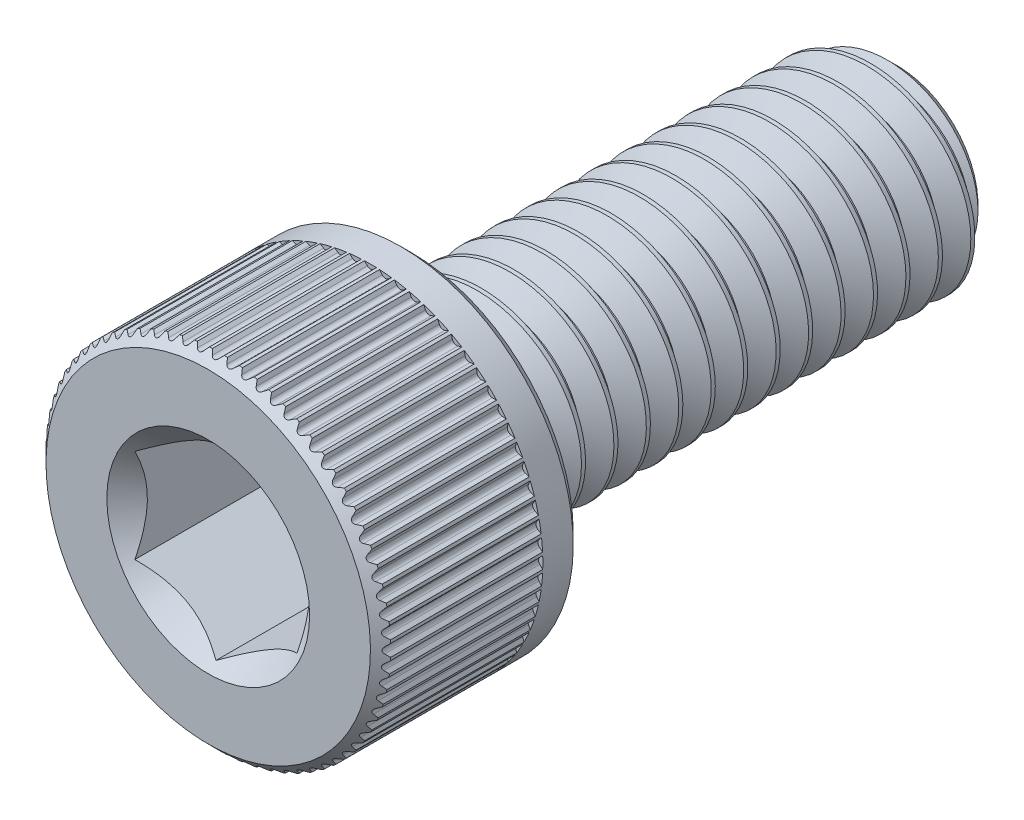
SolidWorks part; units mm, degrees
ref_plane "Front Plane" through (0, 0, 0) normal (0, 0, 1) x (1, 0, 0)
ref_plane "Top Plane" through (0, 0, 0) normal (0, 1, 0) x (1, 0, 0)
ref_plane "Right Plane" through (0, 0, 0) normal (1, 0, 0) x (0, 0, -1)
sketch "Sketch1" plane through (0, 0, 0) normal (1, 0, 0) x (0, 0, -1)
  line L0 (-8.5, 0) -> (8.5, 0) construction
  line L1 (8.5, 0) -> (8.5, 1.9804) construction
  line L2 (8.5, 1.9804) -> (7.9804, 2.5) construction
  line L3 (7.9804, 2.5) -> (7.9, 2.5) construction
  line L4 (7.9, 2.5) -> (-3.5, 2.5) construction
  line L5 (-3.5, 2.5) -> (-3.5, 4.25) construction
  line L6 (-3.5, 4.25) -> (-8.5, 4.25) construction
  line L7 (-8.5, 4.25) -> (-8.5, 0) construction
  line L8 (8.5, 1.9804) -> (8.5, 2.5) construction
  line L9 (8.45, 2.5866) -> (8.85, 1.8938) construction
  line L10 (8.85, 1.8938) -> (9.25, 2.5866) construction
  line L11 (9.25, 2.5866) -> (8.45, 2.5866) construction
  line L12 (8.85, 2.5866) -> (8.85, 2.5) construction
  line L13 (8.85, 1.8938) -> (8.85, 1.9804) construction
  line L14 (8.8, 1.9804) -> (8.9, 1.9804) construction
  line L15 (8.5, 2.5) -> (9.2, 2.5) construction
  line L16 (8.475, 2.5433) -> (9.225, 2.5433) construction
  line L17 (8.5, 0) -> (8.5, -2.5) construction
  line L18 (-3.75, 4.25) -> (-3.5, 4) construction
  line L19 (-8.25, 4.25) -> (-8.5, 4) construction
  line L20 (-3.5, 2.5) -> (-3.5, 0) construction
  line L21 (-3.5, 1.25) -> (0.5, 1.25) construction
  line L22 (0.5, 1.25) -> (4.5, 1.25) construction
  line L23 (4.5, 1.25) -> (8.5, 1.25) construction
  line L24 (0.5, 1.25) -> (0.5, 2.5) construction
  line L25 (0.5, 2.5) -> (0.5, 4.25) construction
  line L26 (4.5, 1.25) -> (4.5, 4.25) construction
  point P0 (-8.5, 2)
  point P3 (6.5, 2.5)
  point P4 (0, 0)
  point P18 (4.5, 2.5)
  point P22 (8.85, 1.9804)
  point P24 (7.9, 2.5)
  point P25 (8.85, 2.5)
  point P28 (8.85, 2.5433)
  point P29 (6.5, -2.5)
  point P30 (0.5, 2.5)
  point P31 (-6, 4.25)
  point P37 (-4.375, 4.25)
  point P38 (-8.125, 4.25)
  point P45 (0.5, 1.25)
  point P46 (4.5, 1.25)
  dimension "D2" = 0.1
  dimension "D7" = 0.25
  dimension "D8" = 0.25
  dimension "D9" = 0.25
  dimension "D10" = 0.125
  dimension "D11" = 0.625
  dimension "Drive Size" = 4
  dimension "Head Diameter" = 8.5
  dimension "Head Height" = 5
  dimension "Thread Pitch" = 0.8
  dimension "Thread Size" = 5
  dimension "Length" = 12
  dimension "D12" = 0.6
  dimension "D4" = 2
  dimension "D3" = 45
sketch "Sketch2" plane through (0, 0, 0) normal (1, 0, 0) x (0, 0, -1)
  line L0 (-8.5, 0) -> (-8.5, 4)
  line L1 (-8.25, 4.25) -> (-3.75, 4.25)
  line L2 (-3.5, 4) -> (-3.5, 2.75)
  line L4 (7.9804, 2.5) -> (8.5, 1.9804)
  line L5 (8.5, 1.9804) -> (8.5, 0)
  line L6 (-3.5, 4.25) -> (-8.5, 4.25) construction
  line L7 (8.5, 0) -> (-8.5, 0)
  line L8 (-8.25, 4.25) -> (-8.5, 4) construction
  line L10 (-8.25, 4.25) -> (-8.5, 4)
  line L14 (-3.75, 4.25) -> (-3.5, 4) construction
  line L16 (-3.75, 4.25) -> (-3.5, 4)
  line L17 (-3.5, 2.5) -> (-3.5, 4.25) construction
  line L19 (-3.25, 2.5) -> (7.9804, 2.5)
  line L20 (7.9, 2.5) -> (-3.5, 2.5) construction
  arc A1 (-3.5, 2.75) -> (-3.25, 2.5) centre (-3.25, 2.75) ccw
  dimension "D3" = 0.25
revolve "Revolve1" add sketch "Sketch2" angle 360 about L7
sketch "Sketch3" plane through (0, 0, 8.5) normal (0, 0, 1) x (1, 0, 0)
  line L1 (2, -1.1547) -> (2, 1.1547)
  line L2 (2, 1.1547) -> (0, 2.3094)
  line L3 (0, 2.3094) -> (-2, 1.1547)
  line L4 (-2, 1.1547) -> (-2, -1.1547)
  line L5 (-2, -1.1547) -> (0, -2.3094)
  line L6 (0, -2.3094) -> (2, -1.1547)
  circle A0 centre (0, 0) radius 2 construction
  circle A1 centre (0, 0) radius 4.25 construction
  circle A2 centre (0, 0) radius 4.25 construction
  circle A3 centre (0, 0) radius 2.3094 construction
  point P13 (0, 0)
extrude "Cut-Extrude1" cut sketch "Sketch3" against normal offset from surface (4 mm away) 1 up to face at (0, 4, 3.5)
sketch "Sketch4" plane through (0, 0, 8.5) normal (0, 0, 1) x (1, 0, 0)
  circle A0 centre (0, 0) radius 2.5
  dimension "D1" = 5
extrude "Cut-Extrude2" cut sketch "Sketch4" against normal up to vertex (2.5 mm away) draft 45
sketch "Sketch11" plane through (0, 0, 0) normal (1, 0, 0) x (0, 0, -1)
  line L0 (-8.5, 0) -> (8.5, 0) construction
  line L1 (-8.5, 0) -> (8.5, 0) construction
  line L2 (-1.25, 0) -> (-1.25, 2.5) construction
  line L3 (7.9, 2.5) -> (-3.5, 2.5) construction
  line L4 (6.25, 0) -> (6.25, 2.5) construction
  line L6 (8.5, 1.9804) -> (8.5, 2.5) construction
  point P2 (-1.25, 0)
  point P3 (6.25, 0)
  dimension "D1" = 2.25
  dimension "D2" = 2.25
sketch "Sketch6" plane through (0, 0, -8.5) normal (0, 0, -1) x (-1, 0, 0)
  circle A0 centre (0, 0) radius 2.5
curve "Helix/Spiral1" pitch 0.8 height 12.8 turns 16
sketch "Sketch10" plane through (0, 0, 0) normal (1, 0, 0) x (0, 0, -1)
  line L0 (-3.25, -4.25) -> (-3.25, 4.25)
  line L5 (-8.5, 0) -> (8.5, 0) construction
  line L6 (-3.25, 2.5) -> (-3.25, -2.5) construction
  point P3 (-3.25, 0)
split "Split1" trim tools "Sketch10" bodies to split 106 resulting bodies 114 115
sketch "Sketch7" plane through (0, 0, 0) normal (1, 0, 0) x (0, 0, -1)
  line L0 (8.475, 2.5433) -> (9.225, 2.5433)
  line L1 (9.225, 2.5433) -> (8.9, 1.9804)
  line L2 (8.9, 1.9804) -> (8.8, 1.9804)
  line L3 (8.8, 1.9804) -> (8.475, 2.5433)
sweep "Cut-Sweep1" cut profiles "Sketch7" path "Helix/Spiral1"
sketch "Sketch8" plane through (0, 0, 0) normal (1, 0, 0) x (0, 0, -1)
  line L0 (-3.5, 0) -> (-3.5, 2.5)
  line L1 (-3.25, -2.5) -> (-3.25, 2.5) construction
  line L2 (-3.5, 2.5) -> (-3.25, 2.5)
  line L4 (-3.25, 2.5) -> (-1.8066, 0)
  line L5 (-1.8066, 0) -> (-3.5, 0)
  line L6 (7.9, 2.5) -> (-3.5, 2.5) construction
  line L7 (-8.5, 0) -> (8.5, 0) construction
  dimension "D1" = 60
revolve "Revolve2" add sketch "Sketch8" angle 360 about L5
ref_plane "Plane1" through (0, 0, 8.5) normal (0, 0, 1) x (1, 0, 0)
sketch "Sketch12" plane through (0, 0, 8.5) normal (0, 0, 1) x (1, 0, 0)
  line L0 (0, 0) -> (0.1483, 4.2474) construction
  line L1 (0, 0) -> (-0.1483, 4.2474) construction
  line L2 (0, 4.1437) -> (0, 4.3563) construction
  line L3 (-0.2572, 4.3563) -> (0.2572, 4.3563)
  line L4 (-0.2572, 4.3563) -> (-0.0762, 4.1753)
  line L5 (0.0762, 4.1753) -> (0.2572, 4.3563)
  circle A0 centre (0, 0) radius 4.25 construction
  arc A1 (-0.0762, 4.1753) -> (0.0762, 4.1753) centre (0, 4.2516) ccw
  point P9 (0, 4.3563)
  point P13 (0, 4.25)
  dimension "D1" = 4
  dimension "D2" = 0.1063
extrude "Cut-Extrude3" cut sketch "Sketch12" against normal blind 4
pattern_circular "CirPattern1" count 72 over 360 about axis through (0, 0, 0) along (0, 0, 1) of "Cut-Extrude3"
equation "\"D2@Sketch1\" = \"Thread Pitch@Sketch1\" / 8"
equation "\"D4@Helix/Spiral1\" = \"Thread Pitch@Sketch1\""
equation "\"D7@Sketch1\" = \"Head Height@Sketch1\" * .05"
equation "\"D8@Sketch1\"=\"D7@Sketch1\""
equation "\"D9@Sketch1\"=\"D7@Sketch1\""
equation "\"D10@Sketch1\"=\"D7@Sketch1\"/2"
equation "\"D11@Sketch1\"=\"D10@Sketch1\"*5"
equation "\"D4@Sketch1\"=\"Thread Pitch@Sketch1\"*2.5"
equation "\"D12@Sketch1\"=\"Thread Pitch@Sketch1\"*.75"
equation "\"D3@Helix/Spiral1\"=\"Length@Sketch1\"+\"Thread Pitch@Sketch1\""
equation "\"D3@Sketch2\" = \"Thread Size@Sketch1\" * 0.05"
equation "\"D1@Sketch11\"=\"Length@Sketch1\"*0.1875"
equation "\"D2@Sketch11\"=\"D1@Sketch11\""
equation "\"D2@Sketch12\"=\"Head Diameter@Sketch1\"*.0125"
equation "\"D1@Cut-Extrude3\"=\"Head Height@Sketch1\"*.8"
equation "\"D1@CirPattern1\"=\"D3@CirPattern1\"/(1.25*\"D1@Sketch12\")"
equation "\"D1@Sketch4\"=\"Drive Size@Sketch1\"*1.25"
